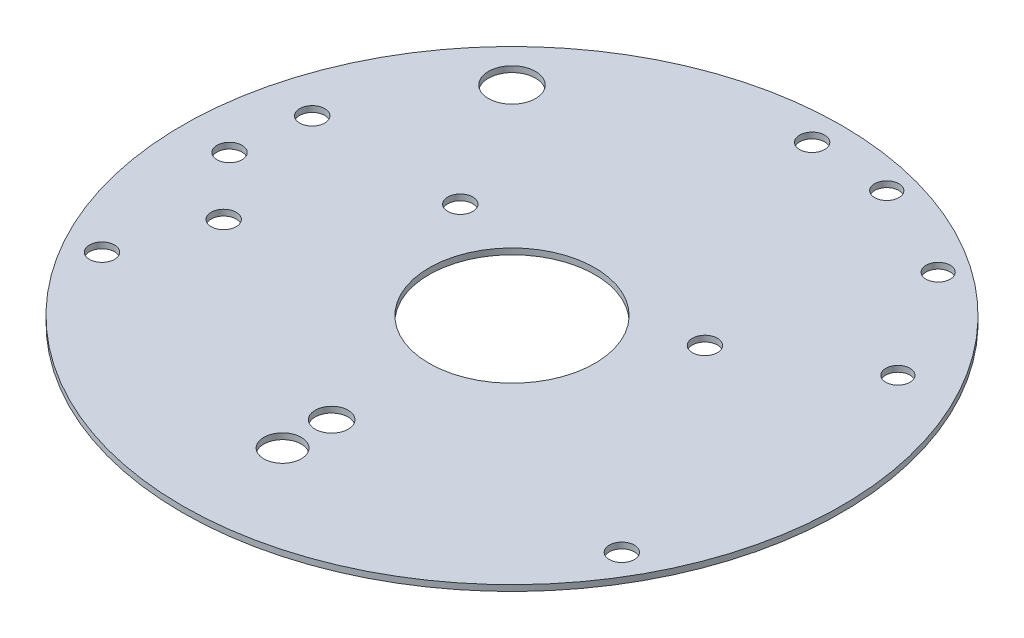
SolidWorks part; units mm, degrees
material "2.1020 (CuSn6)"
ref_plane "Front Plane" through (0, 0, 0) normal (0, 0, 1) x (1, 0, 0)
ref_plane "Top Plane" through (0, 0, 0) normal (0, 1, 0) x (1, 0, 0)
ref_plane "Right Plane" through (0, 0, 0) normal (1, 0, 0) x (0, 0, -1)
sketch "Sketch1" plane through (0, 0, 0) normal (0, 1, 0) x (1, 0, 0)
  circle A0 centre (0, 0) radius 88.9
  circle A1 centre (0, 0) radius 22.352
  circle A2 centre (-53.8734, 53.8734) radius 6.35
  circle A3 centre (0, -61.8998) radius 5.0419
  circle A5 centre (-61.341, -16.4338) radius 3.3782
  circle A6 centre (-76.2, 0) radius 3.3782
  circle A7 centre (-73.6092, 19.7104) radius 3.3782
  circle A8 centre (65.9892, 38.1) radius 3.2639
  circle A10 centre (47.3456, 67.6148) radius 3.2639
  circle A11 centre (21.3614, 79.7306) radius 3.2639
  circle A12 centre (0, 80.9625) radius 3.3782
  circle A13 centre (70.1156, -40.4813) radius 3.3782
  circle A14 centre (-70.1156, -40.4812) radius 3.3782
  circle A16 centre (-32.9956, 19.05) radius 3.3782
  circle A17 centre (32.9956, 19.05) radius 3.3782
  point P32 (0, 0)
  point P39 (0, 0)
  dimension "D1" = 3
extrude "Boss-Extrude1" add sketch "Sketch1" along normal blind 1.6002
sketch "Sketch2" plane through (0, 1.6002, 0) normal (0, 1, 0) x (1, 0, 0)
  circle A0 centre (0, -48.6495) radius 4.445
  point P2 (0, -48.6495)
  dimension "D1" = 8.89
extrude "Cut-Extrude1" cut sketch "Sketch2" against normal blind 2.54
